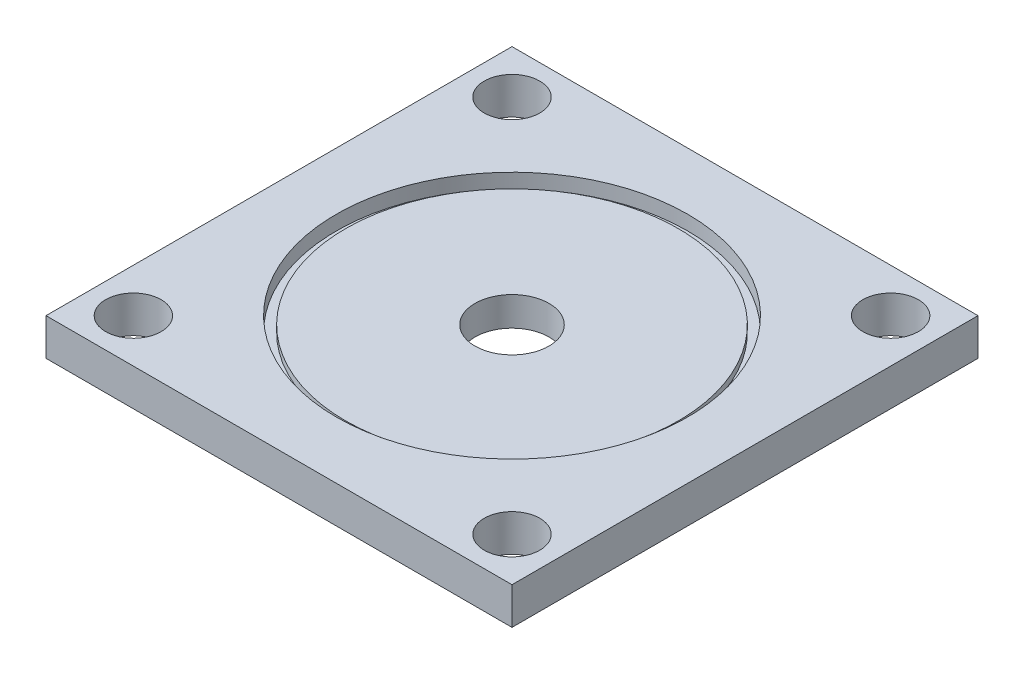
SolidWorks part; units mm, degrees
ref_plane "Front Plane" through (0, 0, 0) normal (0, 0, 1) x (1, 0, 0)
ref_plane "Top Plane" through (0, 0, 0) normal (0, 1, 0) x (1, 0, 0)
ref_plane "Right Plane" through (0, 0, 0) normal (1, 0, 0) x (0, 0, -1)
sketch "plateOutline" plane through (0, 0, 0) normal (0, 1, 0) x (1, 0, 0)
  line L1 (-40, -40) -> (40, -40)
  line L2 (-40, -40) -> (-40, 40)
  line L3 (-40, 40) -> (40, 40)
  line L4 (40, -40) -> (40, 40)
  line L5 (-40, -40) -> (40, 40) construction
  line L6 (-40, 40) -> (40, -40) construction
  line L7 (-40, -40) -> (40, -40) construction
  line L8 (-40, -40) -> (-40, 40) construction
  line L9 (-40, 40) -> (40, 40) construction
  line L10 (40, -40) -> (40, 40) construction
  point P0 (0, 0)
  dimension "D1" = 80
sketch "railGuides" plane through (0, 0, 0) normal (0, 1, 0) x (1, 0, 0)
  line L1 (-32.5, -32.5) -> (32.5, -32.5) construction
  line L2 (-32.5, -32.5) -> (-32.5, 32.5) construction
  line L3 (-32.5, 32.5) -> (32.5, 32.5) construction
  line L4 (32.5, -32.5) -> (32.5, 32.5) construction
  line L6 (-40, 40) -> (-25, 25) construction
  line L7 (40, 40) -> (25, 25) construction
  line L8 (25, -25) -> (40, -40) construction
  line L9 (-40, -40) -> (-25, -25) construction
  line L10 (-40, 40) -> (-25, 25) construction
  circle A0 centre (-32.5, 32.5) radius 4.7625
  circle A1 centre (32.5, 32.5) radius 4.7625
  circle A2 centre (32.5, -32.5) radius 4.7625
  circle A3 centre (-32.5, -32.5) radius 4.7625
sketch "FuelGrainMounting" plane through (0, 0, 0) normal (0, 1, 0) x (1, 0, 0)
  circle A0 centre (0, 0) radius 30.1625
sketch "GasIntake" plane through (0, 0, 0) normal (0, 1, 0) x (1, 0, 0)
  line L0 (-40, 40) -> (40, -40) construction
  circle A0 centre (0, 0) radius 6.35
extrude "Boss-Extrude1" add sketch "plateOutline" along normal blind 6.35 contours L3 L4 L1 L2
extrude "Cut-Extrude1" cut sketch "railGuides" along normal blind 10
extrude "Cut-Extrude2" cut sketch "FuelGrainMounting" along normal blind 5 from offset 5
extrude "Cut-Extrude3" cut sketch "GasIntake" along normal blind 5
sketch "Sketch1" plane through (0, 0, 0) normal (0, 1, 0) x (1, 0, 0)
  circle A0 centre (0, 0) radius 28.575
  circle A2 centre (0, 0) radius 30.1625
  dimension "D1" = 60.325
  dimension "D2" = 57.15
extrude "Cut-Extrude4" cut sketch "Sketch1" against normal blind 1.143 from offset 5
